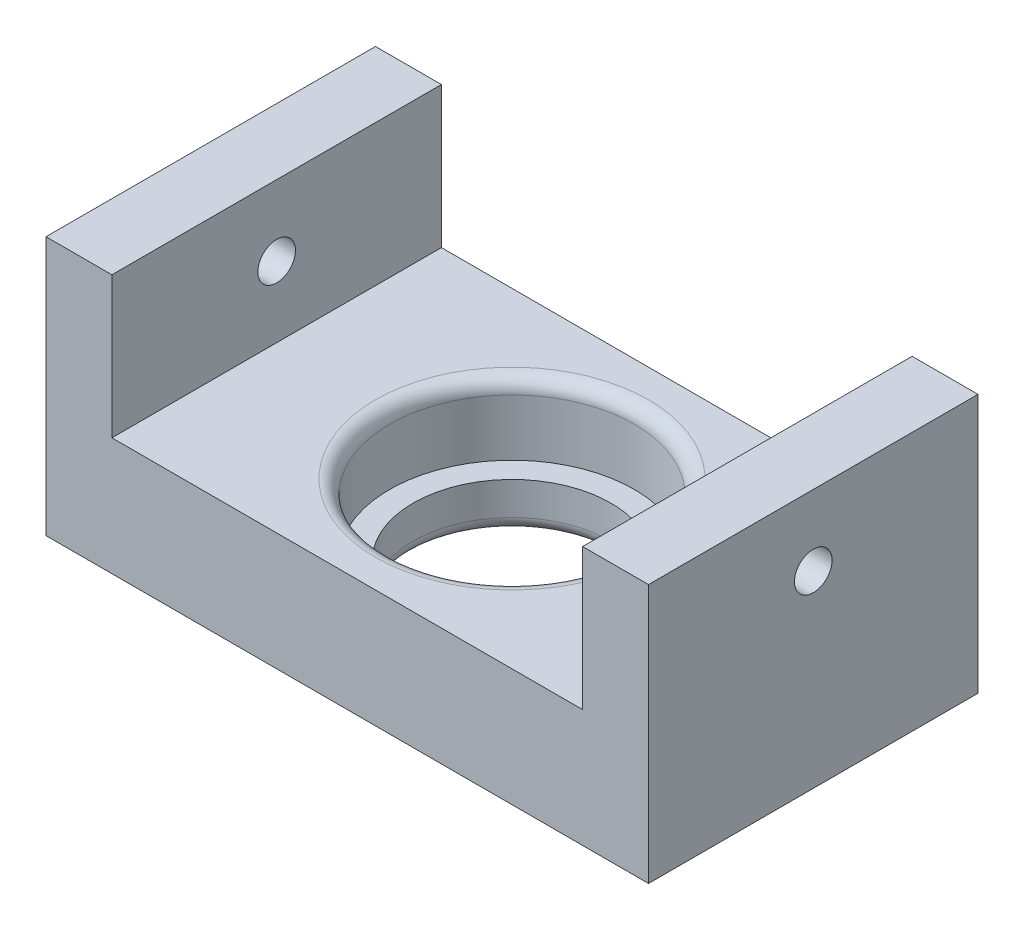
SolidWorks part; units mm, degrees
ref_plane "Front Plane" through (0, 0, 0) normal (0, 0, 1) x (1, 0, 0)
ref_plane "Top Plane" through (0, 0, 0) normal (0, 1, 0) x (1, 0, 0)
ref_plane "Right Plane" through (0, 0, 0) normal (1, 0, 0) x (0, 0, -1)
sketch "Szkic2" plane through (0, 0, 0) normal (0, 0, 1) x (1, 0, 0)
  line L0 (0, 10.5) -> (-32, 10.5)
  line L1 (-32, 10.5) -> (-32, -10.5)
  line L2 (-32, -10.5) -> (0, -10.5)
  line L3 (0, -10.5) -> (32, -10.5)
  line L4 (0, 10.5) -> (32, 10.5)
  line L5 (32, 10.5) -> (32, -10.5)
  line L7 (-32, 10.5) -> (32, 10.5)
  line L8 (-32, 10.5) -> (-32, 17.5)
  line L9 (-32, 17.5) -> (32, 17.5)
  line L10 (32, 10.5) -> (32, 17.5)
  line L11 (-32, -10.5) -> (32, -10.5)
  line L12 (-32, -10.5) -> (-32, -17.5)
  line L13 (-32, -17.5) -> (32, -17.5)
  line L14 (32, -10.5) -> (32, -17.5)
  circle A0 centre (0, 0) radius 10.5
  dimension "D1" = 21
  dimension "D2" = 32
  dimension "D3" = 32
  dimension "D4" = 7
  dimension "D5" = 7
extrude "Dodanie-wyciągnięcie1" add sketch "Szkic2" along normal blind 12.5 contours A0 L0 L1 L2 | A0 L3 L5 L4 | L4 L10 L9 L8 L0 | L14 L3 L2 L12 L13 region at (-20.0077, 0, 0) region at (0, 14, 0) region at (20.0077, 0, 0) region at (0, -14, 0)
sketch "Szkic3" plane through (0, 0, 12.5) normal (0, 0, 1) x (1, 0, 0)
  circle A0 centre (0, 0) radius 13
  dimension "D1" = 26
extrude "Wytnij-wyciągnięcie1" cut sketch "Szkic3" against normal blind 7.5
sketch "Szkic4" plane through (0, 0, 12.5) normal (0, 0, 1) x (1, 0, 0)
  line L0 (-32, -17.5) -> (32, -17.5) construction
  line L1 (-32, 17.5) -> (-25, 17.5)
  line L2 (-32, 17.5) -> (-32, -17.5)
  line L3 (-32, -17.5) -> (-25, -17.5)
  line L4 (-25, 17.5) -> (-25, -17.5)
  line L6 (32, 17.5) -> (25, 17.5)
  line L7 (32, 17.5) -> (32, -17.5)
  line L8 (32, -17.5) -> (25, -17.5)
  line L9 (25, 17.5) -> (25, -17.5)
  dimension "D1" = 7
  dimension "D2" = 7
extrude "Dodanie-wyciągnięcie2" add sketch "Szkic4" along normal blind 15
sketch "Szkic6" plane through (25, 0, 0) normal (-1, 0, 0) x (0, 0, 1)
  circle A0 centre (20, 0) radius 2
  dimension "D1" = 4
extrude "Wytnij-wyciągnięcie2" cut sketch "Szkic6" against normal blind 7 contours A0
sketch "Szkic7" plane through (-25, 0, 0) normal (1, 0, 0) x (0, 0, -1)
  circle A0 centre (-20, 0) radius 2
  dimension "D1" = 4
extrude "Wytnij-wyciągnięcie3" cut sketch "Szkic7" against normal blind 7 contours A0
fillet "Zaokrąglenie2" radius 1.5 1 edges at (13, 0, 12.5)
fillet "Zaokrąglenie3" radius 1.5 1 edges at (10.5, 0, 0)
move or copy body "Obiekt-Przenieś/Kopiuj2" bodies to move or copy 105 copy no rotation origin (0, 0, 13.75) rotation axis (-1, 0, 0) rotation angle 90
